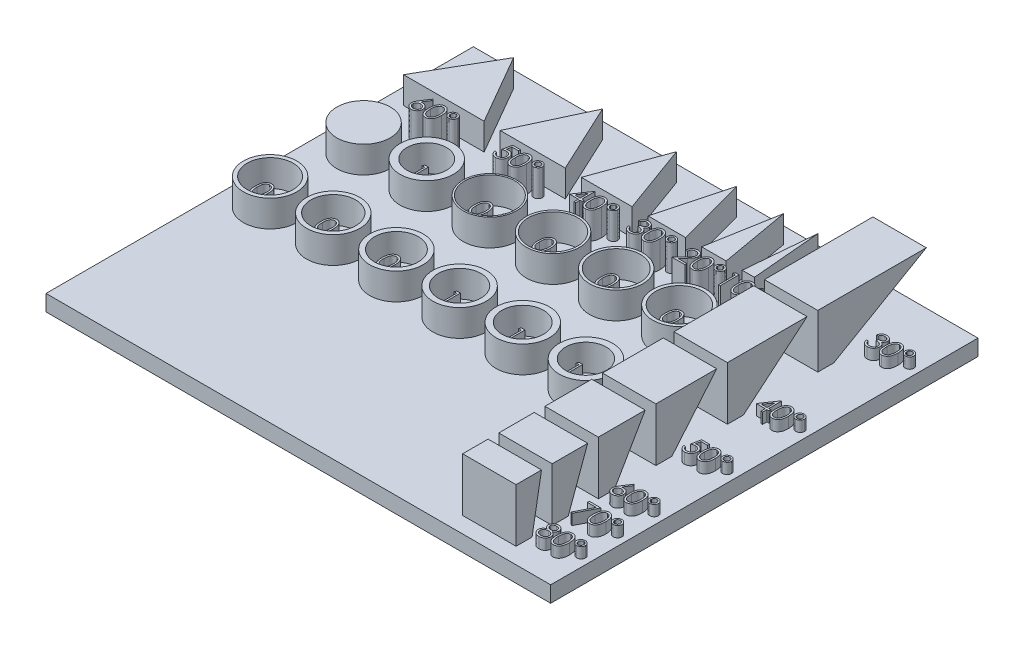
SolidWorks part; units mm, degrees
ref_plane "Front Plane" through (0, 0, 0) normal (0, 0, 1) x (1, 0, 0)
ref_plane "Top Plane" through (0, 0, 0) normal (0, 1, 0) x (1, 0, 0)
ref_plane "Right Plane" through (0, 0, 0) normal (1, 0, 0) x (0, 0, -1)
sketch "Sketch1" plane through (0, 0, 0) normal (0, 1, 0) x (1, 0, 0)
  line L1 (-75, 40) -> (75, 40)
  line L2 (-75, 40) -> (-75, -40)
  line L3 (-75, -40) -> (75, -40)
  line L4 (75, 40) -> (75, -40)
  line L5 (-75, 40) -> (75, -40) construction
  line L6 (-75, -40) -> (75, 40) construction
  point P0 (0, 0)
  dimension "D1" = 150
  dimension "D2" = 80
extrude "Boss-Extrude1" add sketch "Sketch1" along normal blind 3
sketch "Sketch2" plane through (0, 3, 0) normal (0, 1, 0) x (1, 0, 0)
  line L0 (-72, 23.9294) -> (-64.4537, 37)
  line L1 (-64.4537, 37) -> (-56.9073, 23.9294)
  line L2 (-56.9073, 23.9294) -> (-72, 23.9294)
  line L3 (-64.4537, 37) -> (-64.4537, 23.9294) construction
  line L4 (-53.9073, 23.9294) -> (-47.8124, 37)
  line L5 (-47.8124, 37) -> (-41.7175, 23.9294)
  line L6 (-41.7175, 23.9294) -> (-53.9073, 23.9294)
  line L7 (-47.8124, 37) -> (-47.8124, 23.9294) construction
  line L8 (-38.7175, 23.9294) -> (-33.9601, 37)
  line L9 (-33.9601, 37) -> (-29.2028, 23.9294)
  line L10 (-29.2028, 23.9294) -> (-38.7175, 23.9294)
  line L11 (-33.9601, 37) -> (-33.9601, 23.9294) construction
  line L12 (-26.2028, 23.9294) -> (-22.7005, 37)
  line L13 (-22.7005, 37) -> (-19.1983, 23.9294)
  line L14 (-19.1983, 23.9294) -> (-26.2028, 23.9294)
  line L15 (-22.7005, 37) -> (-22.7005, 23.9294) construction
  line L16 (-16.1983, 23.9294) -> (-13.8936, 37)
  line L17 (-13.8936, 37) -> (-11.5889, 23.9294)
  line L18 (-11.5889, 23.9294) -> (-16.1983, 23.9294)
  line L19 (-13.8936, 37) -> (-13.8936, 23.9294) construction
  line L20 (-8.5889, 23.9294) -> (-7.4453, 37)
  line L21 (-7.4453, 37) -> (-6.3018, 23.9294)
  line L22 (-6.3018, 23.9294) -> (-8.5889, 23.9294)
  line L23 (-7.4453, 37) -> (-7.4453, 23.9294) construction
  line L25 (-75, 40) -> (-75, -40) construction
  line L26 (75, 40) -> (-75, 40) construction
  dimension "D1" = 60
  dimension "D2" = 50
  dimension "D3" = 40
  dimension "D4" = 30
  dimension "D5" = 20
  dimension "D6" = 10
  dimension "D7" = 3
  dimension "D8" = 3
  dimension "D9" = 3
  dimension "D10" = 3
  dimension "D11" = 3
  dimension "D12" = 3
  dimension "D13" = 3
extrude "Boss-Extrude2" add sketch "Sketch2" along normal blind 5
sketch "Sketch3" plane through (0, 3, 0) normal (0, 1, 0) x (1, 0, 0)
  text T0 "60°"
extrude "Boss-Extrude3" add sketch "Sketch3" along normal blind 5
sketch "Sketch5" plane through (0, 3, 0) normal (0, 1, 0) x (1, 0, 0)
  text T0 "50°"
extrude "Boss-Extrude4" add sketch "Sketch5" along normal blind 5
sketch "Sketch6" plane through (0, 3, 0) normal (0, 1, 0) x (1, 0, 0)
  text T0 "40°"
extrude "Boss-Extrude5" add sketch "Sketch6" along normal blind 5
sketch "Sketch7" plane through (0, 3, 0) normal (0, 1, 0) x (1, 0, 0)
  text T0 "30°"
extrude "Boss-Extrude6" add sketch "Sketch7" along normal blind 5
sketch "Sketch8" plane through (0, 3, 0) normal (0, 1, 0) x (1, 0, 0)
  text T0 "20°"
extrude "Boss-Extrude7" add sketch "Sketch8" along normal blind 5
sketch "Sketch9" plane through (0, 3, 0) normal (0, 1, 0) x (1, 0, 0)
  text T0 "10°"
extrude "Boss-Extrude8" add sketch "Sketch9" along normal blind 5
sketch "Sketch10" plane through (0, 3, 0) normal (0, 1, 0) x (1, 0, 0)
  line L0 (-68, 12.4511) -> (-56.1746, 12.4511) construction
  line L1 (-56.1746, 12.4511) -> (-44.3492, 12.4511) construction
  line L2 (-44.3492, 12.4511) -> (-32.5239, 12.4511) construction
  line L3 (-32.5239, 12.4511) -> (-20.6985, 12.4511) construction
  line L4 (-20.6985, 12.4511) -> (-8.8731, 12.4511) construction
  line L5 (-68, -5.0472) -> (-56.1746, -5.0472) construction
  line L6 (-56.1746, -5.0472) -> (-44.3492, -5.0472) construction
  line L7 (-44.3492, -5.0472) -> (-32.5239, -5.0472) construction
  line L8 (-32.5239, -5.0472) -> (-20.6985, -5.0472) construction
  line L9 (-20.6985, -5.0472) -> (-8.8731, -5.0472) construction
  line L10 (-75, 40) -> (-75, -40) construction
  line L19 (74.3, -39.3) -> (74.3, 39.3)
  line L20 (74.3, 39.3) -> (-74.3, 39.3)
  line L21 (-74.3, 39.3) -> (-74.3, -39.3)
  line L22 (-74.3, -39.3) -> (74.3, -39.3)
  line L23 (74.3, -39.3) -> (74.3, 39.3)
  line L24 (74.3, 39.3) -> (-74.3, 39.3)
  line L25 (-74.3, 39.3) -> (-74.3, -39.3)
  line L26 (-74.3, -39.3) -> (74.3, -39.3)
  circle A0 centre (-68, 12.4511) radius 5
  circle A1 centre (-56.1746, 12.4511) radius 5
  circle A2 centre (-44.3492, 12.4511) radius 5
  circle A4 centre (-56.1746, 12.4511) radius 3.7
  circle A5 centre (-44.3492, 12.4511) radius 4.7
  circle A6 centre (-32.5239, 12.4511) radius 5
  circle A7 centre (-20.6985, 12.4511) radius 5
  circle A8 centre (-32.5239, 12.4511) radius 4.6
  circle A9 centre (-20.6985, 12.4511) radius 4.5
  circle A10 centre (-8.8731, 12.4511) radius 5
  circle A11 centre (-8.8731, 12.4511) radius 4.4
  circle A12 centre (-68, -5.0472) radius 5
  circle A13 centre (-56.1746, -5.0472) radius 5
  circle A14 centre (-44.3492, -5.0472) radius 5
  circle A15 centre (-32.5239, -5.0472) radius 5
  circle A16 centre (-20.6985, -5.0472) radius 5
  circle A17 centre (-8.8731, -5.0472) radius 5
  circle A18 centre (-68, -5.0472) radius 4.3
  circle A19 centre (-56.1746, -5.0472) radius 4.2
  circle A20 centre (-44.3492, -5.0472) radius 4.1
  circle A21 centre (-32.5239, -5.0472) radius 4
  circle A22 centre (-20.6985, -5.0472) radius 3.9
  circle A23 centre (-8.8731, -5.0472) radius 3.8
  dimension "D1" = 10
  dimension "D2" = 10
  dimension "D3" = 10
  dimension "D7" = 10
  dimension "D8" = 10
  dimension "D11" = 0.6
  dimension "D12" = 10
  dimension "D13" = 7
  dimension "D9" = 0.4
  dimension "D14" = 7
  dimension "D5" = 1.3
  dimension "D6" = 0.3
  dimension "D10" = 0.5
  dimension "D15" = 0.7
  dimension "D16" = 0.7
  dimension "D17" = 0.8
  dimension "D18" = 0.9
  dimension "D19" = 1
  dimension "D20" = 1.1
  dimension "D21" = 1.2
extrude "Boss-Extrude9" add sketch "Sketch10" along normal blind 5 contours A2 A5 | A6 A8 | A10 A11 | A17 A23 | A16 A22 | A15 A21 | A14 A20 | A13 A19 | A12 A18 | A0 | A1 | A4 | A9 | A7 region at (-49.2078, 3, -12.4511) region at (-37.3824, 3, -12.4511) region at (-13.7317, 3, -12.4511) region at (-72.8586, 3, 5.0472) region at (-61.0332, 3, 5.0472) region at (-49.2078, 3, 5.0472) region at (-37.3824, 3, 5.0472) region at (-25.5571, 3, 5.0472) region at (-13.7317, 3, 5.0472)
sketch "Sketch11" plane through (0, 3, 0) normal (0, 1, 0) x (1, 0, 0)
  text T0 "0.1 "
  text T1 "1.3"
  text T2 "0.3\r\n"
  text T3 "0.4"
  text T4 "0.5"
  text T5 "0.6"
  text T6 "0.7"
  text T7 "0.8"
  text T8 "0.9"
  text T9 "1.0"
  text T10 "1.1"
  text T11 "1.2\r\n"
extrude "Boss-Extrude10" add sketch "Sketch11" along normal blind 2
sketch "Sketch12" plane through (0, 0, 0) normal (1, 0, 0) x (0, 0, -1)
  line L0 (-34, 3) -> (-32.2367, 13)
  line L1 (-40, 3) -> (40, 3) construction
  line L2 (-32.2367, 13) -> (-37, 13)
  line L3 (-37, 13) -> (-37, 3)
  line L4 (-37, 3) -> (-34, 3)
  line L5 (-40, 3) -> (-40, 0) construction
  line L6 (-30.2367, 3) -> (-30.2367, 13)
  line L7 (-30.2367, 13) -> (-23.597, 13)
  line L8 (-23.597, 13) -> (-27.2367, 3)
  line L9 (-27.2367, 3) -> (-30.2367, 3)
  line L10 (-21.597, 3) -> (-21.597, 13)
  line L11 (-21.597, 13) -> (-12.8235, 13)
  line L12 (-12.8235, 13) -> (-18.597, 3)
  line L13 (-18.597, 3) -> (-21.597, 3)
  line L14 (-10.8235, 3) -> (-10.8235, 13)
  line L15 (-10.8235, 13) -> (0.5675, 13)
  line L16 (0.5675, 13) -> (-7.8235, 3)
  line L17 (-7.8235, 3) -> (-10.8235, 3)
  line L18 (2.5675, 3) -> (2.5675, 13)
  line L19 (2.5675, 13) -> (17.485, 13)
  line L20 (17.485, 13) -> (5.5675, 3)
  line L21 (5.5675, 3) -> (2.5675, 3)
  line L22 (19.485, 13) -> (19.485, 3)
  line L23 (22.9744, 3) -> (21.1332, 3) construction
  line L24 (19.485, 13) -> (39.8055, 13)
  line L25 (39.8055, 13) -> (22.485, 3)
  line L26 (22.485, 3) -> (19.485, 3)
  line L27 (23.9294, 3) -> (37, 3) construction
  dimension "D1" = 80
  dimension "D2" = 3
  dimension "D3" = 3
  dimension "D4" = 10
  dimension "D5" = 70
  dimension "D6" = 2
  dimension "D7" = 2
  dimension "D8" = 60
  dimension "D9" = 50
  dimension "D10" = 2
  dimension "D11" = 2
  dimension "D12" = 40
  dimension "D13" = 2
  dimension "D14" = 30
extrude "Boss-Extrude11" add sketch "Sketch12" along normal blind 10
sketch "Sketch13" plane through (0, 3, 0) normal (0, 1, 0) x (1, 0, 0)
  text T0 "30°\r\n\r\n\r\n40°\r\n\r\n50°\r\n\r\n60°\r\n70°\r\n80°"
extrude "Boss-Extrude12" add sketch "Sketch13" along normal blind 2
sketch "Sketch14" plane through (0, 3, 0) normal (0, 1, 0) x (1, 0, 0)
  line L1 (19.4805, 50.3274) -> (101.8036, 50.3274)
  line L2 (19.4805, 50.3274) -> (19.4805, -50.3274)
  line L3 (19.4805, -50.3274) -> (101.8036, -50.3274)
  line L4 (101.8036, 50.3274) -> (101.8036, -50.3274)
  line L5 (19.4805, 50.3274) -> (101.8036, -50.3274) construction
  line L6 (19.4805, -50.3274) -> (101.8036, 50.3274) construction
  point P0 (60.642, 0)
extrude "Cut-Extrude1" cut sketch "Sketch14" against normal blind 42
equation "\"`30\"=69.3848"
